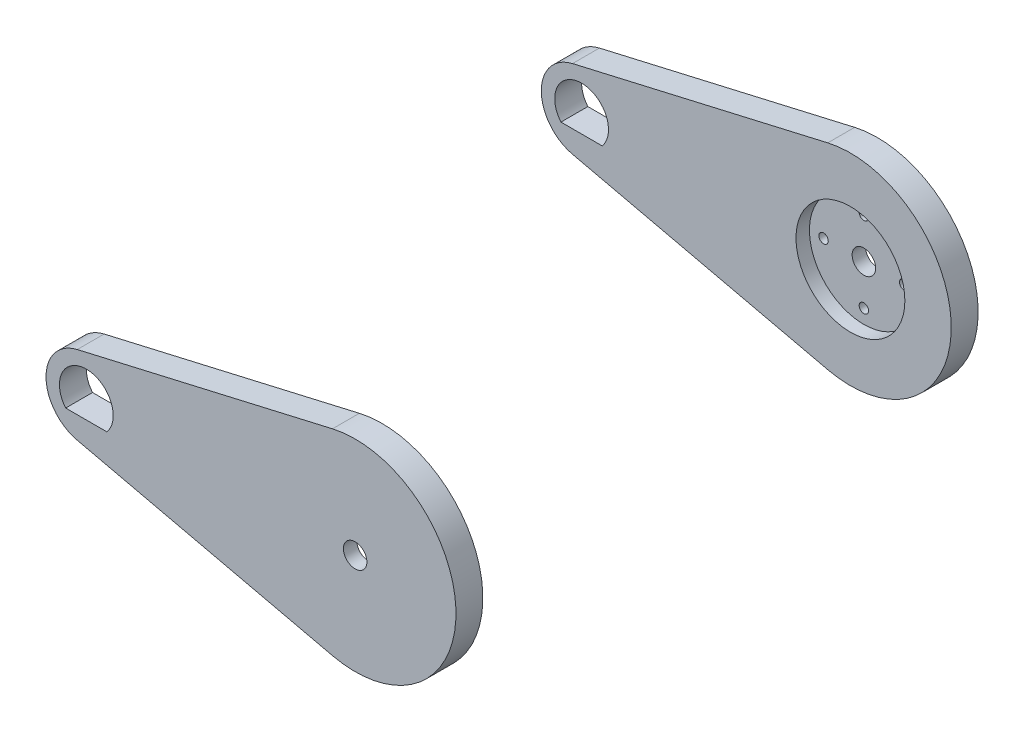
SolidWorks part; units mm, degrees
ref_plane "Front Plane" through (0, 0, 0) normal (0, 0, 1) x (1, 0, 0)
ref_plane "Top Plane" through (0, 0, 0) normal (0, 1, 0) x (1, 0, 0)
ref_plane "Right Plane" through (0, 0, 0) normal (1, 0, 0) x (0, 0, -1)
sketch "Sketch1" plane through (0, 0, 0) normal (0, 0, 1) x (1, 0, 0)
  circle A0 centre (0, 0) radius 15
  circle A10 centre (0, 0) radius 8.1
  circle A11 centre (0, 0) radius 1.75
  point P15 (0, 0)
  point P23 (0, 0)
  dimension "D1" = 30
  dimension "D2" = 16.2
  dimension "D3" = 3.5
extrude "Boss-Extrude1" add sketch "Sketch1" along normal blind 4 contours A0 region at (-14.5757, 0, 0)
extrude "Boss-Extrude2" add sketch "Sketch1<3>" along normal blind 2 contours A10 A11 region at (-7.8709, 0, 0)
sketch "Sketch1<3>" plane through (0, 0, 0) normal (0, 0, 1) x (1, 0, 0) same geometry as "Sketch1"
sketch "Sketch2" plane through (0, 0, 0) normal (0, 0, 1) x (1, 0, 0)
  line L0 (0, 0) -> (-58.5269, 0) construction
  line L1 (-41.35, 5.8462) -> (-3.375, 14.6154)
  line L2 (-41.35, -5.8462) -> (-3.375, -14.6154)
  line L7 (-43.075, -2.5582) -> (-36.925, -2.5582)
  line L8 (-43.075, -2.5582) -> (1.3478, -2.5582) construction
  line L9 (-28.075, -2.5582) -> (-21.925, -2.5582)
  arc A0 (-36.925, -2.5582) -> (-43.075, -2.5582) centre (-40, 0) ccw
  arc A1 (-41.35, 5.8462) -> (-41.35, -5.8462) centre (-40, 0) ccw
  circle A3 centre (0, 0) radius 15 construction
  arc A4 (-21.925, -2.5582) -> (-28.075, -2.5582) centre (-25, 0) ccw
  circle A9 centre (0, 0) radius 15
  arc A10 (-6.925, -2.5582) -> (-13.075, -2.5582) centre (-10, 0) ccw [skipped]
  dimension "D2" = 8
  dimension "D3" = 12
  dimension "D6" = 3
  dimension "D7" = 6.15
  dimension "D1" = 40
extrude "Boss-Extrude3" add sketch "Sketch2" along normal blind 4 contours L1 A1 L2 A4 L9 A0 L7 | L9 A4 region at (-22.2462, 9.7272, 0) region at (-25, 0.4395, 0)
ref_plane "Plane1" through (0, 0, 38.848) normal (0, 0, 1) x (1, 0, 0)
mirror "Mirror2" about plane through (0, 0, 38.848) normal (0, 0, 1) of bodies 103
sketch "Sketch3" plane through (0, 0, 2) normal (0, 0, 1) x (1, 0, 0)
  circle A0 centre (0, 0) radius 6 construction
  circle A1 centre (0, 6) radius 0.7
  circle A2 centre (6, 0) radius 0.7
  circle A3 centre (0, -6) radius 0.7
  circle A4 centre (-6, 0) radius 0.7
  dimension "D1" = 12
  dimension "D2" = 1.4
  dimension "D3" = 1.4
  dimension "D4" = 1.4
  dimension "D5" = 1.4
extrude "Cut-Extrude1" cut sketch "Sketch3" against normal blind 10
